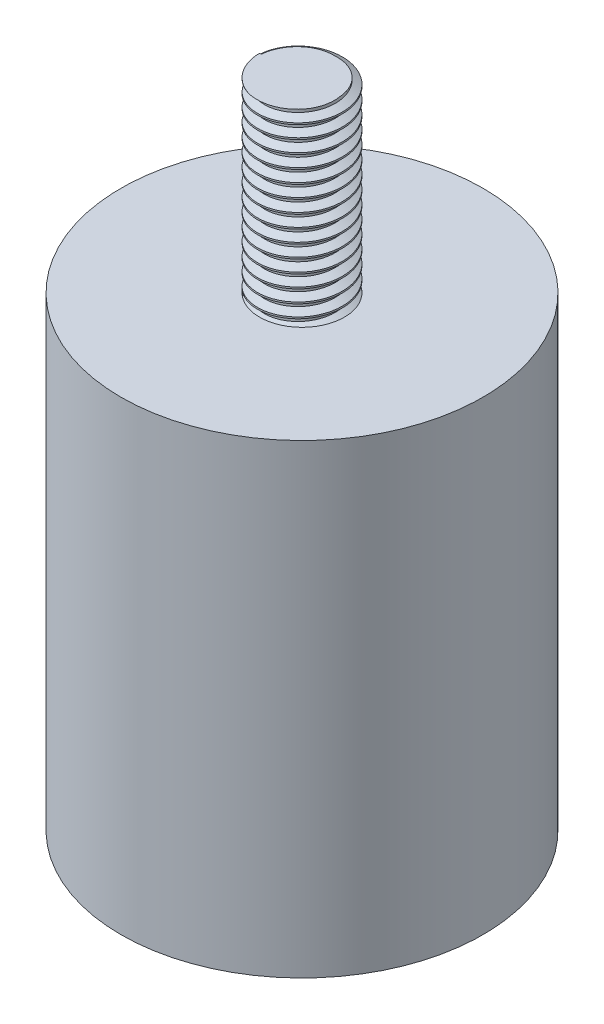
SolidWorks part; units mm, degrees
ref_plane "Front Plane" through (0, 0, 0) normal (0, 0, 1) x (1, 0, 0)
ref_plane "Top Plane" through (0, 0, 0) normal (0, 1, 0) x (1, 0, 0)
ref_plane "Right Plane" through (0, 0, 0) normal (1, 0, 0) x (0, 0, -1)
sketch "Çizim1" plane through (0, 0, 0) normal (0, 0, 1) x (1, 0, 0)
  line L1 (0, 0) -> (17.5, 0)
  line L2 (0, 0) -> (0, 45)
  line L3 (0, 45) -> (17.5, 45)
  line L4 (17.5, 0) -> (17.5, 45)
  line L5 (17.5, 45) -> (13.4, 45)
  line L6 (17.5, 45) -> (17.5, 63)
  line L7 (17.5, 63) -> (13.4, 63)
  line L8 (13.4, 45) -> (13.4, 63)
  dimension "D1" = 17.5
  dimension "D2" = 45
  dimension "D3" = 4.1
  dimension "D4" = 18
revolve "Döndür1" add sketch "Çizim1" angle 360 about L4 region at (8.75, 22.5, 0) region at (15.45, 54, 0)
thread "Diş1" pitch 1.25 method cut profile "Diş Profili1" start angle 0, offset 1, length 0, pitch 1.25, diameter 8.2
ref_plane "Düzlem1" through (13.4, 64, 0) normal (0, 0, 1) x (-1, 0, 0)
sketch "Diş Profili1" plane through (13.4, 64, 0) normal (0, 0, 1) x (-1, 0, 0)
  line L0 (0, 0) -> (0, 1.25) construction
  line L11 (0, 0) -> (0, 1.0937)
  line L12 (0, 1.0937) -> (-0.6766, 0.7031)
  line L13 (-0.6766, 0.7031) -> (-0.6766, 0.3906)
  line L15 (-0.6766, 0.3906) -> (0, 0)
  line L17 (-0.6766, 0.5469) -> (0, 0.5469) construction
  point P2 (0, 0)
  dimension "Pitch" = 1.25
  dimension "Profile_Angle" = 60
  dimension "Profile_Land" = 0.3125
  dimension "Profile_Height" = 0.6766
hole_wizard "M8 Dişli Delik1" positions "Çizim8" profile "Çizim9" tap size "M8" standard "ISO"
sketch "Çizim8" plane through (0, 0, 0) normal (0, -1, 0) x (-1, 0, 0)
  point P0 (-17.5, 0)
sketch "Çizim9" plane through (17.5, 0, 0) normal (1, 0, 0) x (0, 0, -1)
  line L0 (0, 0) -> (0, 17.0429)
  line L1 (0, 17.0429) -> (3.4, 15)
  line L2 (3.4, 15) -> (3.4, 0)
  line L5 (3.4, 0) -> (0, 0)
  line L10 (0, 17.0429) -> (-3.4, 15) construction
  line L11 (0, -6.35) -> (0, 107.95) construction
  dimension "Tap Drill Dia." = 6.8
  dimension "Tap Drill Depth" = 15
  dimension "Drill Angle" = 118
cosmetic thread "Delik Dişi1" parameters "D1"=12, "D2"=8
